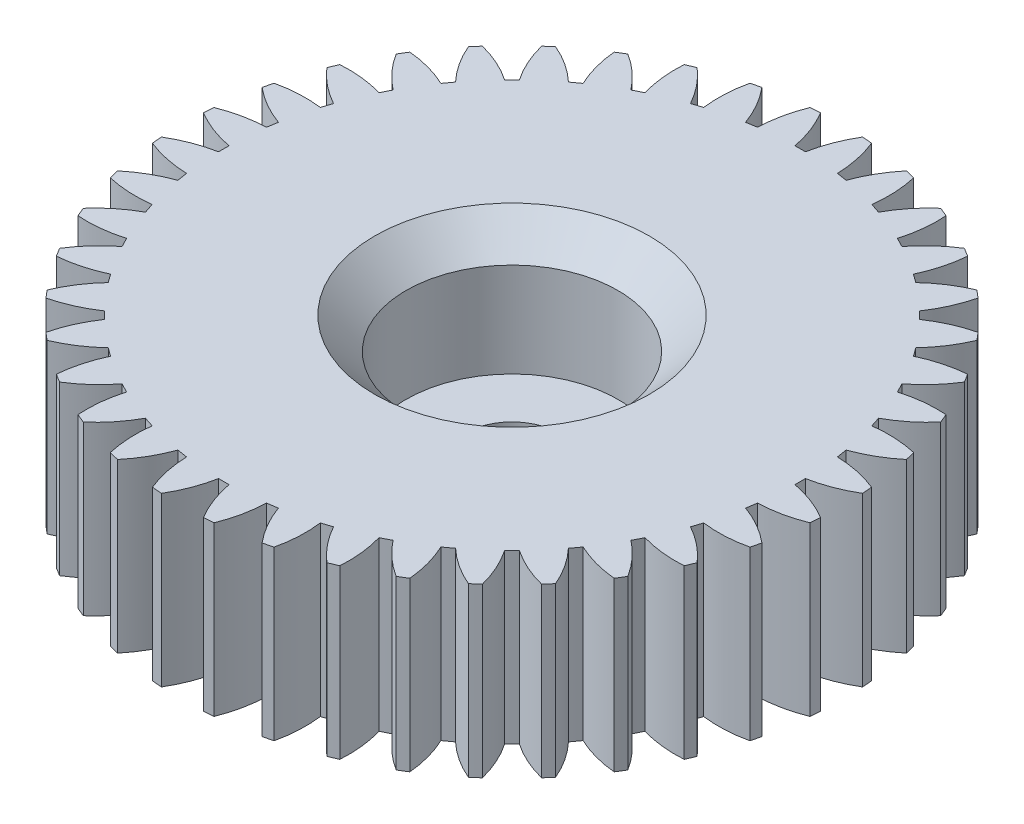
SolidWorks part; units mm, degrees
ref_plane "Front Plane" through (0, 0, 0) normal (0, 0, 1) x (1, 0, 0)
ref_plane "Top Plane" through (0, 0, 0) normal (0, 1, 0) x (1, 0, 0)
ref_plane "Right Plane" through (0, 0, 0) normal (1, 0, 0) x (0, 0, -1)
sketch "Sketch1" plane through (0, 0, 0) normal (0, 1, 0) x (1, 0, 0)
  line L0 (0, 0) -> (0, 7.875) construction
  circle A0 centre (0, 0) radius 7.875
  circle A1 centre (0, 0) radius 6.875
  arc A2 (0.125, 6.8739) -> (0.5, 7.8591) centre (3.0727, 6.3159) cw
  arc A3 (-0.125, 6.8739) -> (-0.5, 7.8591) centre (-3.0727, 6.3159) ccw
  circle A4 centre (0, 0) radius 2.525
  circle A5 centre (0, 0) radius 1.125
  point P8 (0, 6.875)
  point P9 (0, 6.875)
  point P12 (0, 0)
  point P13 (0, 0)
  point P14 (0.183, 6.8726)
  dimension "D1" = 15.75
  dimension "D2" = 1
  dimension "D4" = 3
  dimension "D5" = 5.05
  dimension "D6" = 2.25
  dimension "D3" = 0.5
  dimension "D7" = 0.125
extrude "Boss-Extrude1" add sketch "Sketch1" along normal blind 1 contours A5 A4 region at (-2.4536, 0, 0)
extrude "Boss-Extrude2" add sketch "Sketch1<3>" along normal blind 4 contours A4 A1 | A1 A0 A2 | A0 | A1 region at (-5.2364, 0, 5.5802) region at (4.7666, 0, -4.6807)
sketch "Sketch1<3>" plane through (0, 0, 0) normal (0, 1, 0) x (1, 0, 0) same geometry as "Sketch1"
extrude "Cut-Extrude1" cut sketch "Sketch1<5>" along normal through all contours L0 A0 | L0 A2 A0 region at (0, 0, -7.4836)
sketch "Sketch1<5>" plane through (0, 0, 0) normal (0, 1, 0) x (1, 0, 0) same geometry as "Sketch1"
pattern_circular "CirPattern3" count 40 over 360 about axis through (0, 4, 0) along (0, -1, 0) of "Cut-Extrude1"
fillet "Fillet1" radius 0.4 1 edges at (0, 0, 1.125)
chamfer "Chamfer1" distance 0.75 angle 45 1 edges at (0, 4, 2.525)
